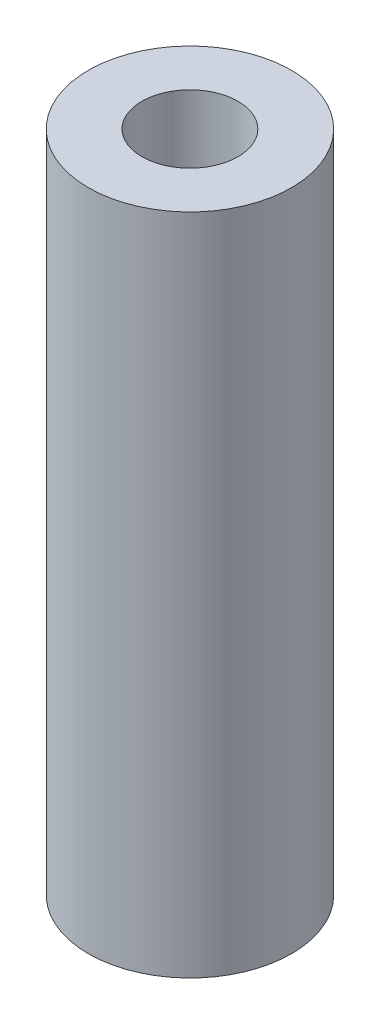
SolidWorks part; units mm, degrees
ref_plane "Front Plane" through (0, 0, 0) normal (0, 0, 1) x (1, 0, 0)
ref_plane "Top Plane" through (0, 0, 0) normal (0, 1, 0) x (1, 0, 0)
ref_plane "Right Plane" through (0, 0, 0) normal (1, 0, 0) x (0, 0, -1)
sketch "Sketch1" plane through (0, 0, 0) normal (0, 1, 0) x (1, 0, 0)
  circle A0 centre (0, 0) radius 5.975
  dimension "D1" = 11.95
extrude "Boss-Extrude1" add sketch "Sketch1" along normal blind 39
sketch "Sketch2" plane through (0, 39, 0) normal (0, 1, 0) x (1, 0, 0)
  circle A0 centre (0, 0) radius 2.825
  dimension "D1" = 5.65
extrude "Cut-Extrude1" cut sketch "Sketch2" against normal blind 9
sketch "Sketch3" plane through (0, 0, 0) normal (0, -1, 0) x (1, 0, 0)
  circle A0 centre (0, 0) radius 9.645
extrude "Cut-Extrude2" [suppressed] cut sketch "Sketch3" against normal blind 25
sketch "Sketch4" plane through (0, 39, 0) normal (0, 1, 0) x (1, 0, 0)
  circle A0 centre (0, 0) radius 5.955
  circle A1 centre (0, 0) radius 3.5804
extrude "Cut-Extrude3" [suppressed] cut sketch "Sketch4" against normal blind 30
